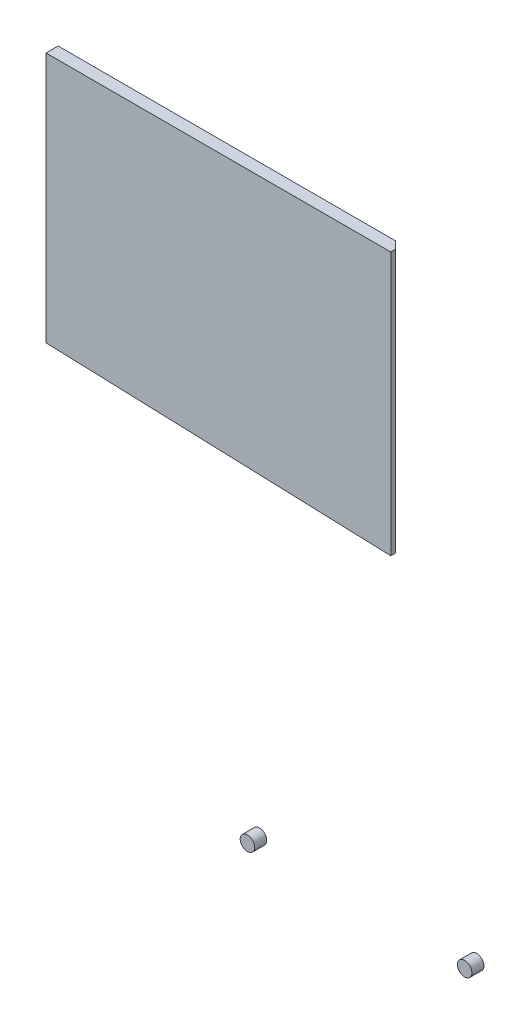
SolidWorks part; units mm, degrees
ref_plane "Спереди" through (0, 0, 0) normal (0, 0, 1) x (1, 0, 0)
ref_plane "Сверху" through (0, 0, 0) normal (0, 1, 0) x (1, 0, 0)
ref_plane "Справа" through (0, 0, 0) normal (1, 0, 0) x (0, 0, -1)
ref_plane "Плоскость4" through (0, 0, 241.9894) normal (0, 0, -1) x (-1, 0, 0)
sketch "Эскиз1" plane through (0, 0, 241.9894) normal (0, 0, -1) x (-1, 0, 0)
  line L0 (95.6767, 9.8587) -> (90.6739, 9.8587)
  line L1 (80.4267, 99.8587) -> (30.9267, 99.8587) construction
  line L2 (-116.1479, 99.8587) -> (-136.1479, 99.8587)
  line L4 (90.6739, 10.8587) -> (95.6767, -9.1413)
  line L5 (111.6767, -9.1413) -> (93.6767, -9.1413) construction
  line L7 (-116.1479, 79.8587) -> (-136.1479, 79.8587)
  line L8 (111.6767, 79.8587) -> (95.6767, 79.8587) construction
  line L9 (-116.1479, 79.8587) -> (-116.1479, 99.8587)
  line L10 (-136.1479, 79.8587) -> (-136.1479, 99.8587)
  line L11 (95.6767, 9.8587) -> (95.6767, -9.1413)
  line L12 (90.6739, 10.8587) -> (90.6739, 9.8587)
  circle A0 centre (105.6767, 89.8587) radius 3
  circle A1 centre (105.6767, -0.1413) radius 3
extrude "Бобышка-Вытянуть1" add sketch "Эскиз1" along normal blind 35 rebuild error yes
ref_plane "Плоскость5" through (0, 0, 206.9894) normal (0, 0, -1) x (-1, 0, 0)
sketch "Эскиз2" plane through (0, 0, 206.9894) normal (0, 0, -1) x (-1, 0, 0)
  line L2 (80.4267, 99.8587) -> (30.9267, 99.8587) construction
  line L3 (-27.1479, 99.8587) -> (115.6767, 99.8587)
  line L5 (-27.1479, 99.8587) -> (-27.1479, -9.1413)
  line L6 (93.6767, -9.1413) -> (67.861, -9.1413) construction
  line L7 (-27.1479, -9.1413) -> (115.6767, -4.1385)
  line L8 (115.6767, -4.1385) -> (115.6767, 99.8587)
  circle A0 centre (32.2349, -141.9659) radius 3
  circle A1 centre (-57.7651, -141.9659) radius 3
extrude "Бобышка-Вытянуть2" add sketch "Эскиз2" along normal blind 5
fillet "Скругление1" radius 4 rebuild error yes
chamfer "Фаска1" distance 3 angle 45 1 edges at (27.1479, 45.3587, 201.9894)
chamfer "Фаска2" distance 2 angle 45 rebuild error yes
